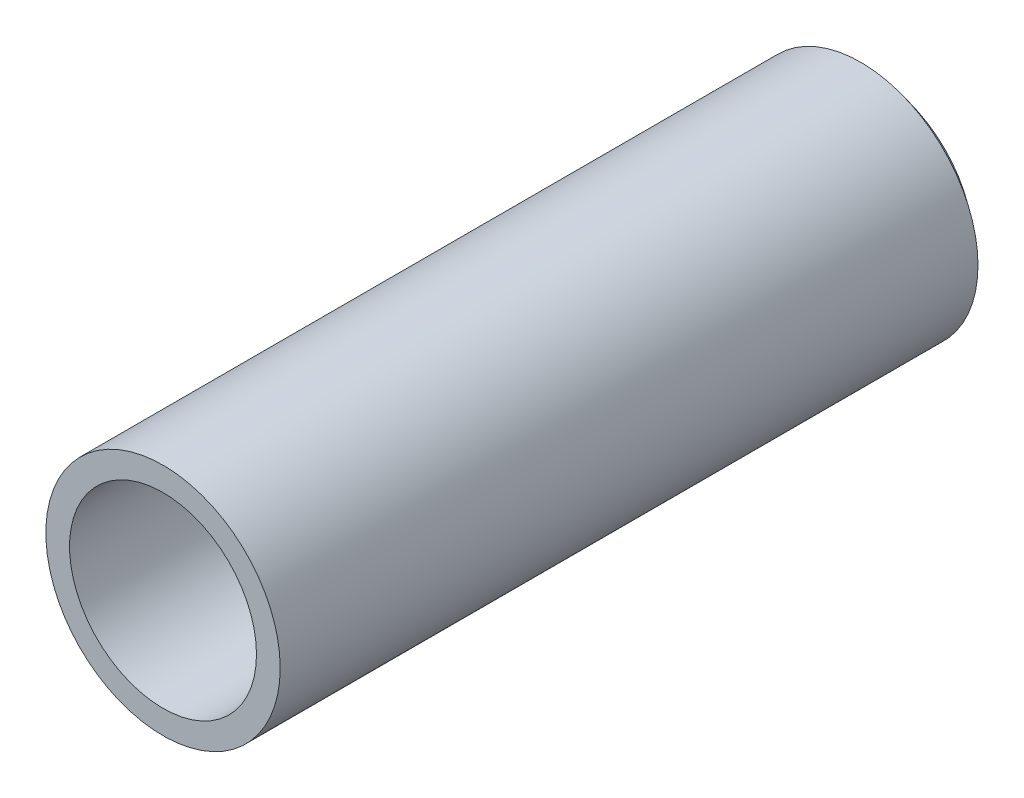
SolidWorks part; units mm, degrees
material "Plain Carbon Steel"
ref_plane "Front Plane" through (0, 0, 0) normal (0, 0, 1) x (1, 0, 0)
ref_plane "Top Plane" through (0, 0, 0) normal (0, 1, 0) x (1, 0, 0)
ref_plane "Right Plane" through (0, 0, 0) normal (1, 0, 0) x (0, 0, -1)
sketch "Sketch1" plane through (0, 0, 0) normal (0, 0, 1) x (1, 0, 0)
  circle A0 centre (0, 0) radius 16.7005
  circle A1 centre (0, 0) radius 13.3223
  dimension "D1" = 33.401
  dimension "D2" = 3.3782
extrude "Extrude1" add sketch "Sketch1" along normal mid plane 101.6
ref_plane "Plane-Origin" through (0, 0, 0) normal (0, 0, 1) x (1, 0, 0)
ref_axis "Axis1" through (0, 0, 50.8) along (0, 0, -1)
chamfer "Chamfer1" [suppressed] distance 3.81 angle 37.5
chamfer "Chamfer2" distance 2.794 angle 37.5 1 edges at (16.7005, 0, -50.8) first distance on face at (16.7005, 0, -50.8)
